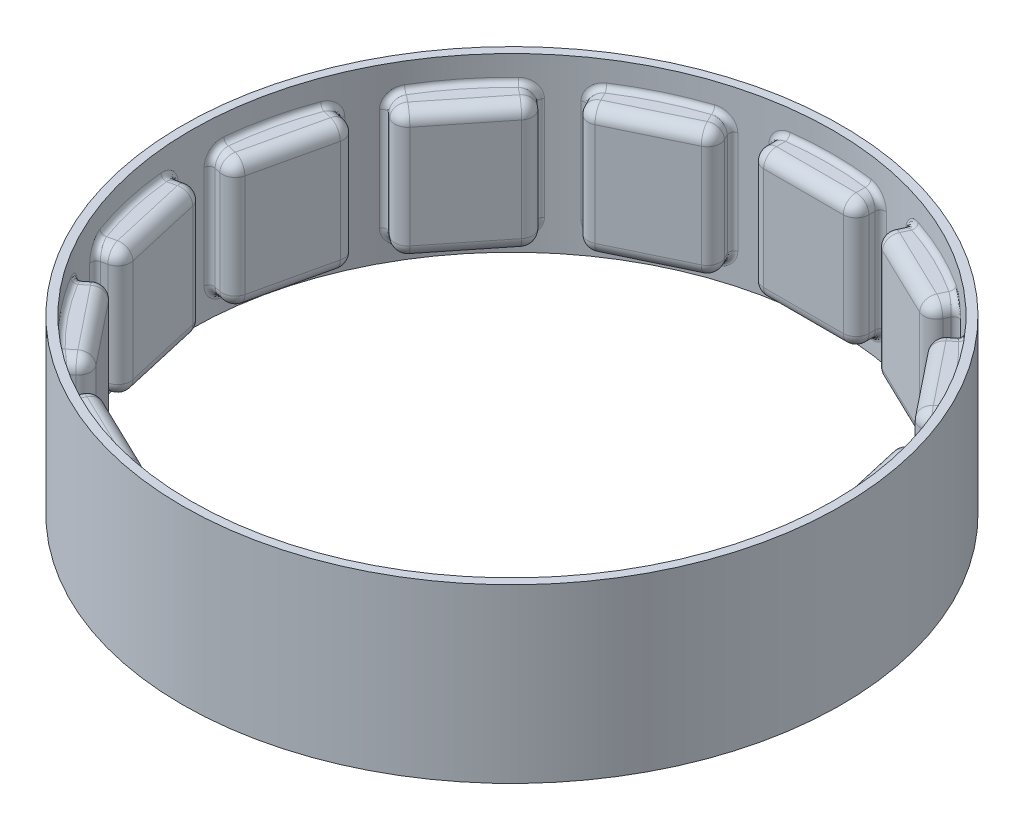
SolidWorks part; units mm, degrees
ref_plane "Front Plane" through (0, 0, 0) normal (0, 0, 1) x (1, 0, 0)
ref_plane "Top Plane" through (0, 0, 0) normal (0, 1, 0) x (1, 0, 0)
ref_plane "Right Plane" through (0, 0, 0) normal (1, 0, 0) x (0, 0, -1)
sketch "Sketch1" plane through (0, 0, 0) normal (0, 1, 0) x (1, 0, 0)
  circle A0 centre (0, 0) radius 12.83
  circle A1 centre (0, 0) radius 12.5
  dimension "D1" = 25.66
  dimension "D2" = 25
extrude "Boss-Extrude1" add sketch "Sketch1" along normal blind 6.7
sketch "Sketch2" plane through (0, 6.7, 0) normal (0, 1, 0) x (1, 0, 0)
  line L1 (-2.05, 11.3492) -> (2.05, 11.3492)
  line L2 (-2.05, 11.3492) -> (-2.05, 12.5492)
  line L3 (-2.05, 12.5492) -> (2.05, 12.5492)
  line L4 (2.05, 11.3492) -> (2.05, 12.5492)
  line L5 (-2.05, 11.3492) -> (2.05, 12.5492) construction
  line L6 (-2.05, 12.5492) -> (2.05, 11.3492) construction
  circle A0 centre (0, 0) radius 11 construction
  point P0 (0, 11.9492)
  dimension "D2" = 22
  dimension "D1" = 4.1
  dimension "D3" = 1.2
extrude "Boss-Extrude2" add sketch "Sketch2" against normal blind 5 from offset 1 separate body offset against normal yes
fillet "Fillet1" radius 0.5 8 edges at (2.05, 3.2, -11.3492) (0, 0.7, -11.3492) (-2.05, 3.2, -11.3492) (0, 5.7, -11.3492) (-2.05, 0.7, -11.9492) (-2.05, 5.7, -11.9492) (2.05, 0.7, -11.9492) (2.05, 5.7, -11.9492)
pattern_circular "CirPattern1" count 14 over 360 about axis through (0, 6.7, 0) along (0, -1, 0) of bodies 102
combine bodies "Combine4" operation type add bodies to combine 102 101 113 112 111 110 109 108 107 106 105 104 103 116 117
fillet "Fillet2" radius 0.2 112 edges at (-11.8648, 4.8476, 3.9341) (-11.5654, 3.2, 4.7425) (-11.595, 0.9327, 4.6697) (-12.1866, 0.7, 2.7815) (-12.4682, 0.8482, 0.8915) (-12.4778, 3.2, 0.7452) (-12.4708, 5.5094, 0.8536) (-12.3967, 4.8476, -1.6034) (-12.4778, 3.2, -0.7452) (-12.4728, 0.9327, -0.8236) (-12.1866, 0.7, -2.7815) (-11.6202, 0.8482, -4.6066) (-11.5654, 3.2, -4.7425) (-11.6062, 5.5094, -4.6418) (1.1953, 4.8476, -12.4427) (2.05, 3.2, -12.3308) (1.9725, 0.9327, -12.3434) (0, 0.7, -12.5) (-1.9053, 0.8482, -12.3539) (-2.05, 3.2, -12.3308) (-1.9428, 5.5094, -12.3481) (3.683, 5.5887, -11.9451) (3.5031, 3.2, -11.9991) (3.6072, 0.8906, -11.9682) (5.4235, 0.7, -11.2621) (7.0427, 0.8113, -10.3271) (7.1971, 3.2, -10.2202) (7.108, 5.5094, -10.2823) (8.5011, 5.5887, -9.1642) (8.3624, 3.2, -9.2909) (8.4428, 0.8906, -9.2179) (9.7729, 0.7, -7.7936) (10.8261, 0.8113, -6.2487) (10.9187, 3.2, -6.0853) (10.8654, 5.5094, -6.18) (11.8648, 4.8476, -3.9341) (11.5654, 3.2, -4.7425) (11.595, 0.9327, -4.6697) (12.1866, 0.7, -2.7815) (12.4682, 0.8482, -0.8915) (12.4778, 3.2, -0.7452) (12.4708, 5.5094, -0.8536) (12.3967, 4.8476, 1.6034) (12.4778, 3.2, 0.7452) (12.4728, 0.9327, 0.8236) (12.1866, 0.7, 2.7815) (11.6202, 0.8482, 4.6066) (11.5654, 3.2, 4.7425) (11.6062, 5.5094, 4.6418) (-8.5011, 5.5887, 9.1642) (-8.3624, 3.2, 9.2909) (-8.4428, 0.8906, 9.2179) (-9.7729, 0.7, 7.7936) (-10.8261, 0.8113, 6.2487) (-10.9187, 3.2, 6.0853) (-10.8654, 5.5094, 6.18) (-3.683, 5.5887, 11.9451) (-3.5031, 3.2, 11.9991) (-3.6072, 0.8906, 11.9682) (-5.4235, 0.7, 11.2621) (-7.0427, 0.8113, 10.3271) (-7.1971, 3.2, 10.2202) (-7.108, 5.5094, 10.2823) (0, 5.7, 12.5) (-1.9428, 5.5094, 12.3481) (-2.05, 3.2, 12.3308) (-1.9053, 0.8482, 12.3539) (0, 0.7, 12.5) (1.9725, 0.9327, 12.3434) (2.05, 3.2, 12.3308) (9.7729, 5.7, 7.7936) (8.4428, 5.5094, 9.2179) (8.3624, 3.2, 9.2909) (8.5011, 0.8113, 9.1642) (9.7729, 0.7, 7.7936) (10.8654, 0.8906, 6.18) (10.9187, 3.2, 6.0853) (7.0427, 5.5887, 10.3271) (5.4235, 5.7, 11.2621) (3.6072, 5.5094, 11.9682) (3.5031, 3.2, 11.9991) (3.683, 0.8113, 11.9451) (5.4235, 0.7, 11.2621) (7.108, 0.8906, 10.2823) (-12.1866, 5.7, 2.7815) (-12.1866, 5.7, -2.7815) (0, 5.7, -12.5) (5.4235, 5.7, -11.2621) (9.7729, 5.7, -7.7936) (12.1866, 5.7, -2.7815) (12.1866, 5.7, 2.7815) (-9.7729, 5.7, 7.7936) (-5.4235, 5.7, 11.2621) (1.1953, 4.8476, 12.4427) (10.8261, 5.5887, 6.2487) (7.1971, 3.2, 10.2202) (-7.108, 0.8906, -10.2823) (-7.1971, 3.2, -10.2202) (-7.0427, 5.5887, -10.3271) (-5.4235, 5.7, -11.2621) (-3.6072, 5.5094, -11.9682) (-3.5031, 3.2, -11.9991) (-3.683, 0.8113, -11.9451) (-10.8654, 0.8906, -6.18) (-10.9187, 3.2, -6.0853) (-10.8261, 5.5887, -6.2487) (-9.7729, 5.7, -7.7936) (-8.4428, 5.5094, -9.2179) (-8.3624, 3.2, -9.2909) (-8.5011, 0.8113, -9.1642) (-5.4235, 0.7, -11.2621) (-9.7729, 0.7, -7.7936)
